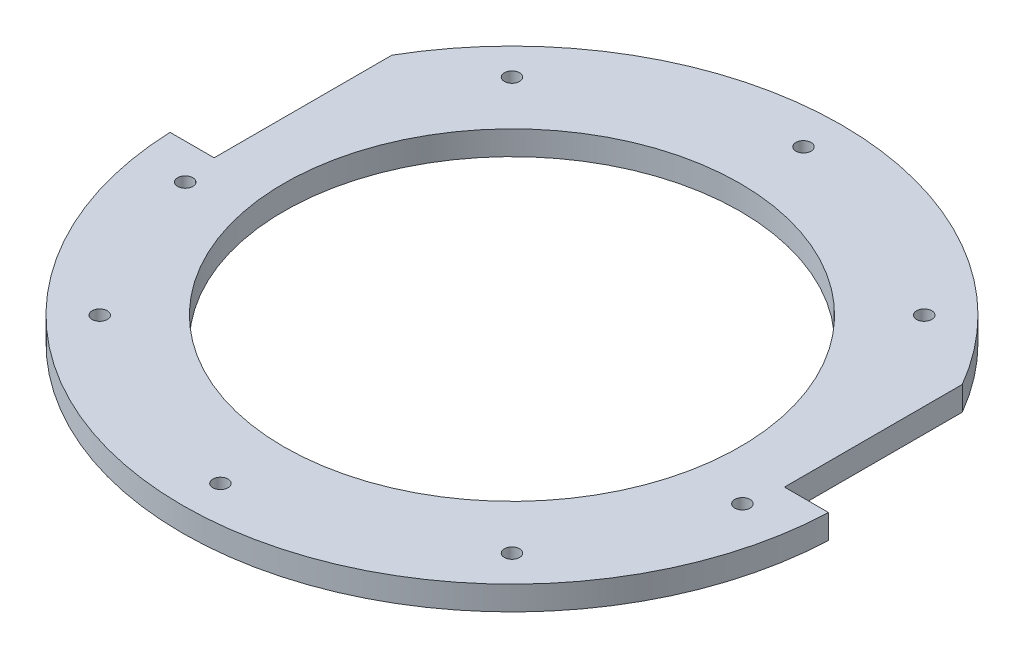
SolidWorks part; units mm, degrees
note: '?' marks a value the reader was unsure of.
ref_plane "Front Plane" through (0, 0, 0) normal (0, 0, 1) x (1, 0, 0)
ref_plane "Top Plane" through (0, 0, 0) normal (0, 1, 0) x (1, 0, 0)
ref_plane "Right Plane" through (0, 0, 0) normal (1, 0, 0) x (0, 0, -1)
sketch "Sketch1" plane through (0, 0, 0) normal (0, 1, 0) x (1, 0, 0)
  line L0 (0, -45) -> (0, 45) construction
  line L1 (-45, 0) -> (45, 0) construction
  line L2 (-40.6586, -40.6586) -> (40.6586, 40.6586) construction
  line L3 (-40.6586, 40.6586) -> (40.6586, -40.6586) construction
  line L4 (40.6586, -40.6586) -> (45.9619, -45.9619) construction
  line L6 (0, -65) -> (0, -57.5) construction
  line L7 (40.6586, 40.6586) -> (45.9619, 45.9619) construction
  circle A1 centre (0, 0) radius 65
  circle A2 centre (0, -57.5) radius 1.5
  circle A3 centre (40.6586, -40.6586) radius 1.5
  circle A5 centre (40.6586, 40.6586) radius 1.5
  circle A6 centre (0, 57.5) radius 1.5
  circle A8 centre (-40.6586, 40.6586) radius 1.5
  circle A9 centre (-40.6586, -40.6586) radius 1.5
  circle A10 centre (0, 0) radius 45
  point P7 (0, 0)
  point P10 (0, 0)
  point P13 (0, 0)
  point P16 (0, 0)
extrude "Boss-Extrude1" add sketch "Sketch1" along normal blind 4.75
sketch "Sketch3" plane through (0, 4.75, 0) normal (0, 1, 0) x (1, 0, 0)
  line L1 (-65, 0) -> (-61.25, 0) construction
  line L7 (56.25, 2.5) -> (56.25, -2.5)
  line L8 (-66.25, 2.5) -> (-56.25, 2.5)
  line L12 (-66.25, 2.5) -> (-66.25, -2.5)
  line L13 (-66.25, -2.5) -> (-56.25, -2.5)
  line L14 (-56.25, 2.5) -> (-56.25, -2.5)
  line L15 (-66.25, 2.5) -> (-56.25, -2.5) construction
  line L16 (-66.25, -2.5) -> (-56.25, 2.5) construction
  line L17 (66.25, -2.5) -> (56.25, -2.5)
  line L18 (66.25, 2.5) -> (66.25, -2.5)
  line L19 (66.25, 2.5) -> (56.25, 2.5)
  circle A2 centre (0, 0) radius 65 construction
extrude "Cut-Extrude1" cut sketch "Sketch3" against normal blind 5
sketch "Sketch4" plane through (0, 4.75, 0) normal (0, 1, 0) x (1, 0, 0)
  line L0 (-56.25, 2.5) -> (-56.25, 32.572)
  line L1 (0, 0) -> (0, 30) construction
  line L2 (-56.25, 2.5) -> (-64.9519, 2.5)
  line L3 (56.25, 2.5) -> (64.9519, 2.5)
  line L4 (56.25, 2.5) -> (56.25, 32.572)
  arc A0 (64.9519, 2.5) -> (-64.9519, 2.5) centre (0, 0) ccw construction
  arc A1 (64.9519, 2.5) -> (-64.9519, 2.5) centre (0, 0) ccw
  line M5 (56.25, 2.5) -> (64.9519, 2.5)
  arc M6 (64.9519, 2.5) -> (-64.9519, 2.5) centre (0, 0) ccw
  line M7 (-64.9519, 2.5) -> (-56.25, 2.5)
extrude "Cut-Extrude2" cut sketch "Sketch4" against normal through all contours L0 M7 M6 | L4 M5 M6
sketch "Sketch5" plane through (0, 0, 0) normal (0, -1, 0) x (1, 0, 0)
  line L0 (0, 0) -> (0, 21.2269) construction
  circle A0 centre (54.9519, 9.5) radius 1.5
  circle A1 centre (-54.9519, 9.5) radius 1.5
extrude "Cut-Extrude3" cut sketch "Sketch5" against normal through all
convert to sheet metal "Convert-Solid1" [suppressed] bend radius? 10 thickness? 4.75
sketch "Bend-Lines1" [suppressed] plane through (0, 0, 0) normal (0, 1, 0) x (1, 0, 0)
sketch "Bounding-Box1" [suppressed] plane through (0, 0, 0) normal (0, 1, 0) x (1, 0, 0)
sheet metal parameters "Sheet-Metal5" thickness 4.75 parameters "D1"=10
flat pattern "Flat-Pattern5" [suppressed]
sketch "Bend-Lines2" plane through (0, 0, 0) normal (0, 1, 0) x (1, 0, 0)
sketch3d "Bounding-Box2" [suppressed]
  line L0 (78.74, 47.4343, 0) -> (47.4343, -78.74, 0) construction
  line L1 (-44.9481, 78.1232, 0) -> (-76.2538, -48.0511, 0) construction
  line L2 (78.74, 47.4343, 0) -> (-44.9481, 78.1232, 0) construction
  line L3 (47.4343, -78.74, 0) -> (-76.2538, -48.0511, 0) construction
